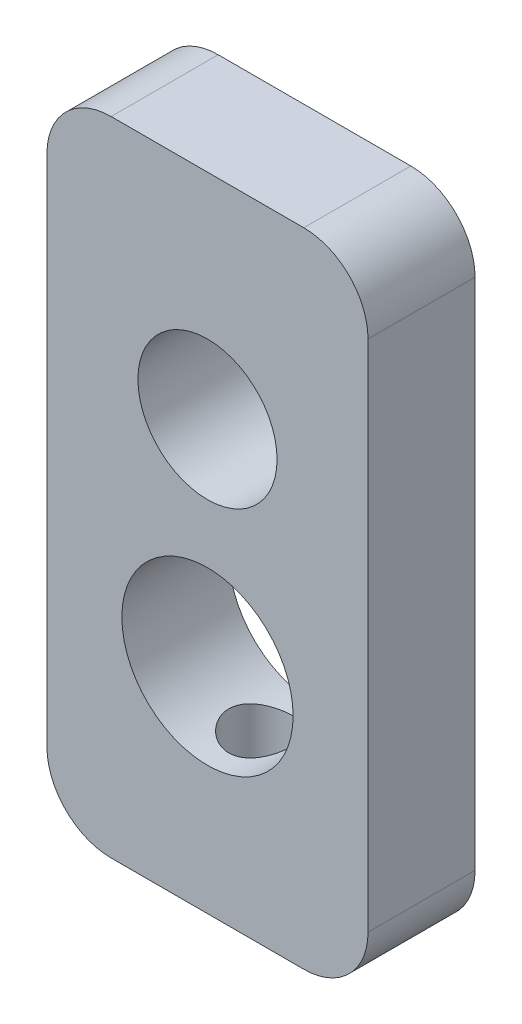
SolidWorks part; units mm, degrees
material "6061 Alloy"
ref_plane "Front Plane" through (0, 0, 0) normal (0, 0, 1) x (1, 0, 0)
ref_plane "Top Plane" through (0, 0, 0) normal (0, 1, 0) x (1, 0, 0)
ref_plane "Right Plane" through (0, 0, 0) normal (1, 0, 0) x (0, 0, -1)
sketch "Sketch1" plane through (0, 0, 0) normal (0, 0, 1) x (1, 0, 0)
  line L1 (-7.5, 20) -> (7.5, 20)
  line L2 (-7.5, 20) -> (-7.5, -10)
  line L3 (-7.5, -10) -> (7.5, -10)
  line L4 (7.5, 20) -> (7.5, -10)
  circle A1 centre (0, 0) radius 4
  dimension "D1" = 8
  dimension "D2" = 10
  dimension "D3" = 15
  dimension "D4" = 7.5
  dimension "D5" = 30
extrude "Boss-Extrude1" add sketch "Sketch1" along normal blind 5
sketch "Sketch2" plane through (0, -24.3792, 5) normal (0, 0, -1) x (1, 0, 0)
  line L0 (0, -27.1292) -> (0, -21.6292) construction
  circle A0 centre (0, -34.3792) radius 3.25
  circle A1 centre (0, -24.3792) radius 4 construction
  dimension "D1" = 6.5
  dimension "D2" = 10
sketch "Sketch3" plane through (0, 0, 0) normal (0, 1, 0) x (0, 0, -1)
  line L1 (0, 8.5759) -> (0, -8.5759) construction
  line L2 (-2.75, 0) -> (2.75, 0) construction
  circle A0 centre (-2.5, 0) radius 1.5
  dimension "D1" = 3
  dimension "D2" = 2.5
extrude "Cut-Extrude1" cut sketch "Sketch3" against normal blind 30
extrude "Cut-Extrude2" cut sketch "Sketch2" along normal blind 10
fillet "Fillet1" radius 3 4 edges at (7.5, -10, 2.5) (-7.5, -10, 2.5) (-7.5, 20, 2.5) (7.5, 20, 2.5)
